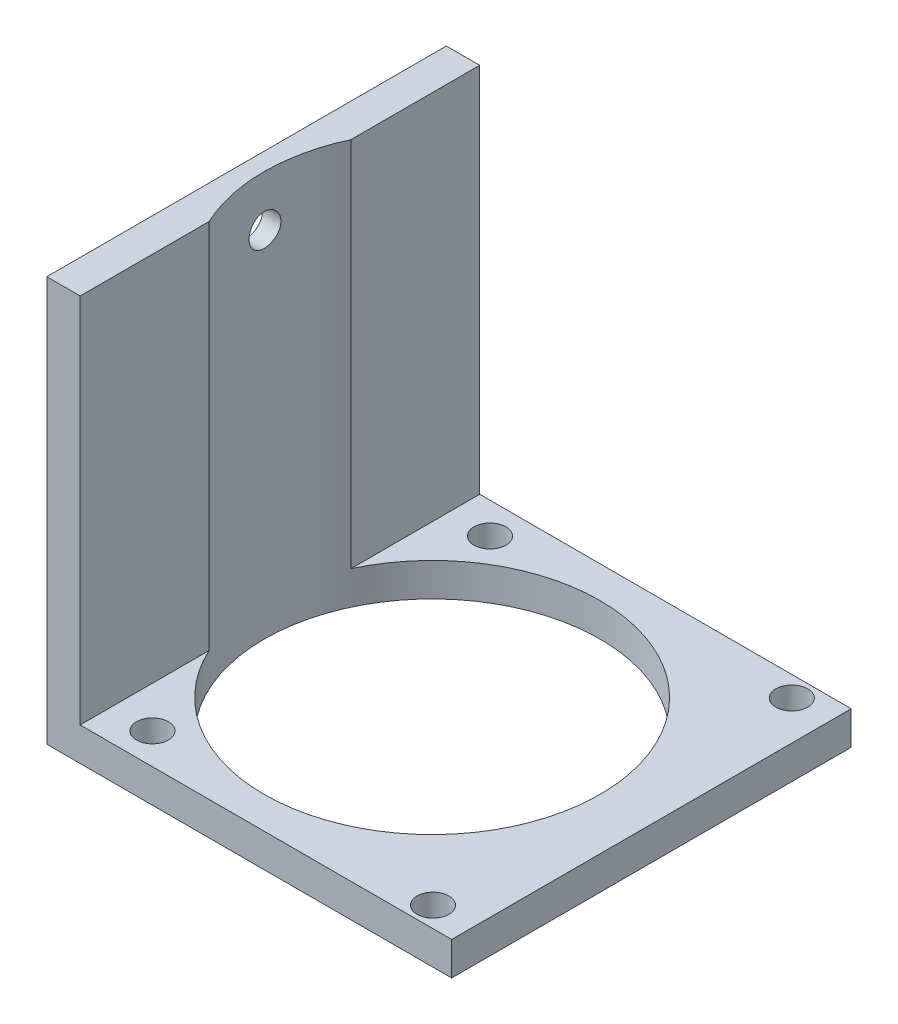
SolidWorks part; units mm, degrees
ref_plane "Front" through (0, 0, 0) normal (0, 0, 1) x (1, 0, 0)
ref_plane "Top" through (0, 0, 0) normal (0, 1, 0) x (1, 0, 0)
ref_plane "Right" through (0, 0, 0) normal (1, 0, 0) x (0, 0, -1)
sketch "Sketch1" plane through (0, 0, 0) normal (0, 0, 1) x (1, 0, 0)
  line L0 (0, 0) -> (38.1, 0)
  line L1 (38.1, 0) -> (38.1, 3.14)
  line L2 (38.1, 3.14) -> (3.14, 3.14)
  line L3 (3.14, 3.14) -> (3.14, 38.1)
  line L4 (3.14, 38.1) -> (0, 38.1)
  line L5 (0, 38.1) -> (0, 0)
extrude "Extrude1" add sketch "Sketch1" along normal blind 37.6
sketch "Sketch2" plane through (0, 3.14, 0) normal (0, 1, 0) x (-1, 0, 0)
  circle A0 centre (-34.425, 35.68) radius 1.5
  circle A1 centre (-17.4625, 18.8) radius 15.8
  circle A2 centre (-34.425, 1.92) radius 1.5
  circle A3 centre (-7.025, 34.68) radius 1.5
  circle A4 centre (-7.025, 2.92) radius 1.5
extrude "Cut-Extrude1" cut sketch "Sketch2" against normal through all and the other way through all
sketch "Sketch3" plane through (0, 0, 0) normal (-1, 0, 0) x (0, 0, 1)
  circle A0 centre (18.8, 33.3375) radius 1.5
extrude "Cut-Extrude2" cut sketch "Sketch3" against normal through all
